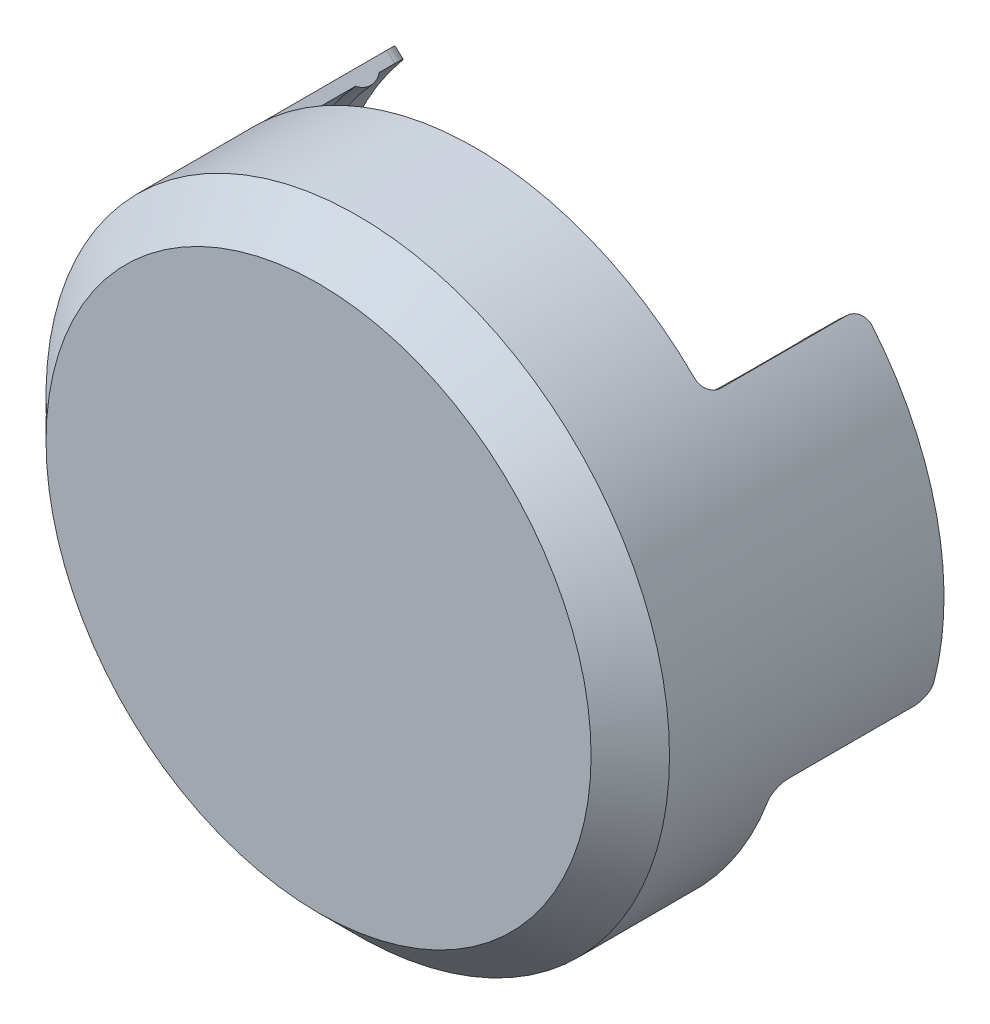
SolidWorks part; units mm, degrees
note: '?' marks a value the reader was unsure of.
ref_plane "Front Plane" through (0, 0, 0) normal (0, 0, 1) x (1, 0, 0)
ref_plane "Top Plane" through (0, 0, 0) normal (0, 1, 0) x (1, 0, 0)
ref_plane "Right Plane" through (0, 0, 0) normal (1, 0, 0) x (0, 0, -1)
sketch "Sketch1" plane through (0, 0, 0) normal (0, 0, 1) x (1, 0, 0)
  circle A0 centre (0, 0) radius 33.25
  circle A1 centre (0, 0) radius 39.75
  circle A2 centre (0, 0) radius 38.25 construction
  dimension "D1" = 76.5
  dimension "D2" = 1.5
  dimension "D3" = 5
extrude "Boss-Extrude1" add sketch "Sketch1" along normal blind 15
sketch "Sketch2" plane through (0, 0, 15) normal (0, 0, 1) x (1, 0, 0)
  circle A0 centre (0, 0) radius 39.75
  circle A1 centre (0, 0) radius 39.75 construction
extrude "Boss-Extrude2" add sketch "Sketch2" along normal blind 5
sketch "Sketch3" plane through (0, 0, 0) normal (0, 1, 0) x (1, 0, 0)
  line L0 (33.25, -15) -> (-33.25, -15) construction
  line L1 (33.25, -15) -> (-33.25, -15) construction
  line L3 (0, 0) -> (0, -7) construction
  line L4 (0, -15) -> (0, -24.4918) construction
  line L5 (22.5, -15) -> (0, -15)
  line L6 (0, -15) -> (0, -7)
  arc A0 (22.5, -15) -> (0, -7) centre (0, -42.6406) ccw
  point P4 (22.5, -15)
  dimension "D2" = 8
  dimension "D1" = 45
revolve "Revolve3" add sketch "Sketch3" angle 360 about L3
sketch "Sketch6" plane through (0, 0, 0) normal (1, 0, 0) x (0, 0, -1)
  line L0 (0, 39.75) -> (20, 39.75)
  line L1 (20, 39.75) -> (20, 38.35)
  line L2 (20, 38.35) -> (16, 38.35)
  line L5 (0, 33.25) -> (0, 39.75)
  line L6 (13, 38.35) -> (7, 38.35)
  line L7 (13, 38.35) -> (17.5468, 33.8032) construction
  arc A0 (7, 38.35) -> (0, 33.25) centre (7, 30.9961) ccw
  arc A1 (16, 38.35) -> (13, 38.35) centre (14.5, 39.85) cw
  dimension "D1" = 1.4
  dimension "D2" = 7
  dimension "D3" = 20
  dimension "D4" = 45
  dimension "D5" = 3
  dimension "D6" = 4
ref_axis "Axis2" through (0, 0, 15) along (0, 0, -1)?
revolve "Revolve7" add sketch "Sketch6" angle 360
sketch "Sketch7" plane through (0, 0, -20) normal (0, 0, -1) x (-1, 0, 0)
  line L0 (0, 0) -> (0, 17.5057) construction
  line L1 (0, 0) -> (-29.3068, 26.8547)
  line L2 (0, 0) -> (-37.9102, -11.9531)
  line L3 (11.9531, -37.9102) -> (0, 0)
  line L4 (0, 0) -> (37.9102, -11.9531)
  line L5 (-11.9531, -37.9102) -> (0, 0)
  line L6 (0, 0) -> (29.3068, 26.8547)
  line L7 (0, 0) -> (20.8952, -20.8952) construction
  line L9 (0, 0) -> (-14.2573, -14.2573) construction
  arc A0 (11.9531, -37.9102) -> (37.9102, -11.9531) centre (0, 0) ccw
  circle A1 centre (0, 0) radius 39.75 construction
  arc A2 (29.3068, 26.8547) -> (-29.3068, 26.8547) centre (0, 0) ccw
  arc A3 (-37.9102, -11.9531) -> (-11.9531, -37.9102) centre (0, 0) ccw
  point P4 (-28.1075, -28.1075)
  dimension "D1" = 95
  dimension "D2" = 55
  dimension "D3" = 90
ref_plane "Plane1" through (0, 0, 0) normal (0, 0, 1) x (1, 0, 0)
extrude "Cut-Extrude1" cut sketch "Sketch7" against normal up to surface (20 mm away)
fillet "Fillet3" radius 2 12 edges at (37.2426, -11.7426, -20) (28.7907, 26.3818, -20) (-28.7907, 26.3818, -20) (-37.2426, -11.7426, -20) (-11.7426, -37.2426, -20) (11.7426, -37.2426, -20) (-26.9106, 24.659, 0) (26.9106, 24.659, 0) (-10.9758, -34.8107, 0) (-34.8107, -10.9758, 0) (10.9758, -34.8107, 0) (34.8107, -10.9758, 0)
chamfer "Chamfer1" distance 5 angle 45 1 edges at (39.75, 0, 20)
